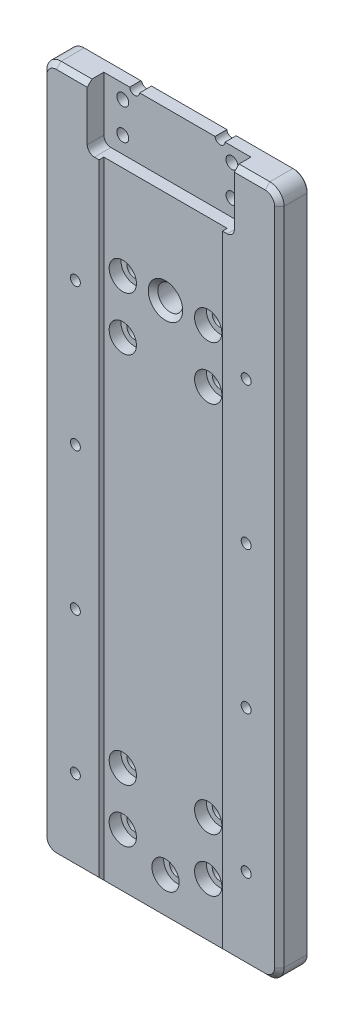
SolidWorks part; units mm, degrees
material "1060 Alloy"
ref_plane "Front Plane" through (0, 0, 0) normal (0, 0, 1) x (1, 0, 0)
ref_plane "Top Plane" through (0, 0, 0) normal (0, 1, 0) x (1, 0, 0)
ref_plane "Right Plane" through (0, 0, 0) normal (1, 0, 0) x (0, 0, -1)
sketch "Sketch1" plane through (0, 0, 0) normal (0, 0, 1) x (1, 0, 0)
  line L1 (50, -145) -> (-50, -145)
  line L2 (50, -145) -> (50, 145)
  line L3 (50, 145) -> (-50, 145)
  line L4 (-50, -145) -> (-50, 145)
  line L5 (50, -145) -> (-50, 145) construction
  line L6 (50, 145) -> (-50, -145) construction
  point P0 (0, 0)
  dimension "D1" = 100
  dimension "D2" = 290
extrude "Boss-Extrude1" add sketch "Sketch1" along normal mid plane 12
sketch "Sketch2" plane through (0, 0, 6) normal (0, 0, 1) x (1, 0, 0)
  line L0 (0, 132) -> (0, 0) construction
  line L1 (31, 119) -> (-31, 119)
  line L2 (31, 119) -> (31, 145)
  line L3 (31, 145) -> (-31, 145)
  line L4 (-31, 119) -> (-31, 145)
  line L5 (31, 119) -> (-31, 145) construction
  line L6 (31, 145) -> (-31, 119) construction
  line L7 (50, 145) -> (-50, 145) construction
  point P0 (0, 132)
  dimension "D1" = 62
  dimension "D2" = 26
extrude "Cut-Extrude1" cut sketch "Sketch2" against normal blind 7
sketch "Sketch3" plane through (0, 0, 6) normal (0, 0, 1) x (1, 0, 0)
  line L0 (-50, -145) -> (50, -145) construction
  line L1 (26, 145) -> (-26, 145)
  line L2 (26, 145) -> (26, -145)
  line L3 (26, -145) -> (-26, -145)
  line L4 (-26, 145) -> (-26, -145)
  line L5 (26, 145) -> (-26, -145) construction
  line L6 (26, -145) -> (-26, 145) construction
  point P0 (0, 0)
  dimension "D1" = 52
extrude "Cut-Extrude2" cut sketch "Sketch3" against normal blind 2
sketch "Sketch4" plane through (0, 0, -6) normal (0, 0, 1) x (1, 0, 0)
  line L0 (0, 132.5) -> (0, 0) construction
  line L1 (23, 126) -> (-23, 126) construction
  line L2 (23, 126) -> (23, 139) construction
  line L3 (23, 139) -> (-23, 139) construction
  line L4 (-23, 126) -> (-23, 139) construction
  line L5 (23, 126) -> (-23, 139) construction
  line L6 (23, 139) -> (-23, 126) construction
  line L7 (31, 145) -> (-31, 145) construction
  line L8 (-18, 145.14) -> (-18, 57.14) construction
  line L9 (-36, 145) -> (-36, -110) construction
  line L10 (-31, 145) -> (-50, 145) construction
  line L11 (-50, -145) -> (-26, -145) construction
  line L12 (0, 0) -> (0, -145) construction
  line L13 (-26, -145) -> (26, -145) construction
  line L14 (50, 45.14) -> (-50, 45.14) construction
  line L15 (18, -100) -> (-18, -100) construction
  line L16 (18, -100) -> (18, -122.5) construction
  line L17 (18, -122.5) -> (-18, -122.5) construction
  line L18 (-18, -100) -> (-18, -122.5) construction
  line L19 (18, -100) -> (-18, -122.5) construction
  line L20 (18, -122.5) -> (-18, -100) construction
  line L21 (50, 45.14) -> (50, 135.14) construction
  line L22 (50, 135.14) -> (-50, 135.14) construction
  line L23 (-50, 45.14) -> (-50, 135.14) construction
  line L24 (50, 45.14) -> (-50, 135.14) construction
  line L25 (50, 135.14) -> (-50, 45.14) construction
  circle A0 centre (-23, 139) radius 2.5
  circle A1 centre (23, 139) radius 2.5
  circle A2 centre (23, 126) radius 2.5
  circle A3 centre (-23, 126) radius 2.5
  circle A4 centre (0, 79.64) radius 5.25
  circle A5 centre (-18, 145.14) radius 2.1
  circle A6 centre (-18, 79.64) radius 3.3
  circle A7 centre (-18, 57.14) radius 3.3
  circle A9 centre (-36, 70) radius 2.1
  circle A10 centre (-36, 58.75) radius 2.1 construction
  circle A11 centre (-36, 10) radius 2.1
  circle A12 centre (-36, -110) radius 2.1
  circle A13 centre (-36, -50) radius 2.1
  circle A14 centre (-18, -100) radius 3.3
  circle A15 centre (-18, -122.5) radius 3.3
  circle A16 centre (18, -100) radius 3.3
  circle A17 centre (18, -122.5) radius 3.3
  circle A18 centre (0, -130) radius 3.3
  circle A20 centre (36, 70) radius 2.1
  circle A21 centre (36, 58.75) radius 2.1 construction
  circle A22 centre (18, 145.14) radius 2.1
  circle A23 centre (18, 57.14) radius 3.3
  circle A24 centre (18, 79.64) radius 3.3
  circle A25 centre (36, 10) radius 2.1
  circle A26 centre (36, -50) radius 2.1
  circle A27 centre (36, -110) radius 2.1
  point P0 (0, 132.5)
  point P36 (0, -111.25)
  point P68 (0, 90.14)
  dimension "D1" = 5
  dimension "D5" = 10.5
  dimension "D12" = 4.2
  dimension "D19" = 6.6
  dimension "D9" = 6.6
  dimension "D2" = 13
  dimension "D3" = 46
  dimension "D4" = 6
  dimension "D8" = 18
  dimension "D10" = 22.5
  dimension "D11" = 36
  dimension "D13" = 35
  dimension "D14" = 60
  dimension "D15" = 60
  dimension "D16" = 48.75
  dimension "D17" = 11.25
  dimension "D20" = 15
  dimension "D21" = 36
  dimension "D23" = 22.5
  dimension "D24" = 100
  dimension "D25" = 90
  dimension "D7" = 10
  dimension "D6" = 12
  dimension "D18" = 190.14
  dimension "D22" = 7.5
extrude "Cut-Extrude HOLES" cut sketch "Sketch4" along normal blind 21
fillet "Fillet1" radius 3 2 edges at (31, 119, 2.5) (-31, 119, 2.5)
fillet "Fillet2" radius 6 4 edges at (50, -145, 0) (-50, -145, 0) (50, 145, 0) (-50, 145, 0)
chamfer "Chamfer1" distance 2 angle 45 10 edges at (35, -145, 6) (48.2426, -143.2426, 6) (50, 0, 6) (48.2426, 143.2426, 6) (37.5, 145, 6) (-35, -145, 6) (-48.2426, -143.2426, 6) (-50, 0, 6) (-48.2426, 143.2426, 6) (-37.5, 145, 6)
sketch "Sketch5" plane through (0, 0, 4) normal (0, 0, 1) x (1, 0, 0)
  circle A1 centre (-18, 79.64) radius 5.75
  circle A2 centre (-18, 57.14) radius 5.75
  circle A3 centre (18, 57.14) radius 5.75
  circle A4 centre (18, 79.64) radius 5.75
  circle A6 centre (18, -100) radius 5.75
  circle A7 centre (-18, -100) radius 5.75
  circle A8 centre (-18, -122.5) radius 5.75
  circle A9 centre (0, -130) radius 5.75
  circle A10 centre (18, -122.5) radius 5.75
  dimension "D1" = 11.5
extrude "Cut-Extrude5" cut sketch "Sketch5" against normal blind 5
chamfer "Chamfer2" distance 2 angle 45 1 edges at (-5.25, 79.64, 4)
chamfer "Chamfer3" distance 0.3 angle 45 8 edges at (-50, 0, -6) (-48.2426, -143.2426, -6) (-48.2426, 143.2426, -6) (0, -145, -6) (48.2426, -143.2426, -6) (48.2426, 143.2426, -6) (50, 0, -6) (-32.0477, 145, -6)
equation "\"M5_tap\"=4.2mm"
equation "\"M5_clearence\"=5.5mm"
equation "\"M6_tap\"=5mm"
equation "\"M6_clearence\"=6.6mm"
equation "\"D1@Sketch4\"=\"M6_tap\""
equation "\"D12@Sketch4\"=\"M5_tap\""
equation "\"D19@Sketch4\"=\"M6_clearence\""
equation "\"work_area_width\"=1100mm"
equation "\"work_area_depth\"=900mm"
equation "\"steel_base_width\"=80mm"
equation "\"steel_base_height\"=50mm"
equation "\"steel_base_wall_thickness\"=3mm"
equation "\"steel_base_radius\"=6mm"
equation "\"steel_sides_width\"=180mm"
equation "\"steel_sides_height\"=50mm"
equation "\"steel_sides_wall_thickness\"=5mm"
equation "\"steel_sides_radius\"=6mm"
equation "\"steel_gantry_width\"=120mm"
equation "\"steel_gantry_height\"=80mm"
equation "\"steel_gantry_wall_thickness\"=6mm"
equation "\"steel_gantry_radius\"=6mm"
equation "\"steel_rollers_width\"=80mm"
equation "\"steel_rollers_height\"=50mm"
equation "\"steel_rollers_wall_thickness\"=6mm"
equation "\"steel_rollers_radius\"=6mm"
equation "\"steel_zbox_width\"=400mm"
equation "\"steel_zbox_height\"=90mm"
equation "\"steel_zbox_wall_thickness\"=3mm"
equation "\"steel_zbox_radius\"=6mm"
equation "\"alu_zangle_width\"=400mm"
equation "\"alu_zangle_height\"=50mm"
equation "\"alu_zangle_wall_thickness\"=10mm"
equation "\"D9@Sketch4\"=\"M6_clearence\""
equation "\"D25@Sketch4\"=\"steel_zbox_height\""
equation "\"D6@Sketch4\"=\"steel_zbox_radius\"*2"
equation "\"D18@Sketch4\"=\"steel_gantry_width\" + \"alu_zangle_wall_thickness\" + 60.14"
equation "\"D20@Sketch4\"=\"alu_zangle_wall_thickness\" + 5"
